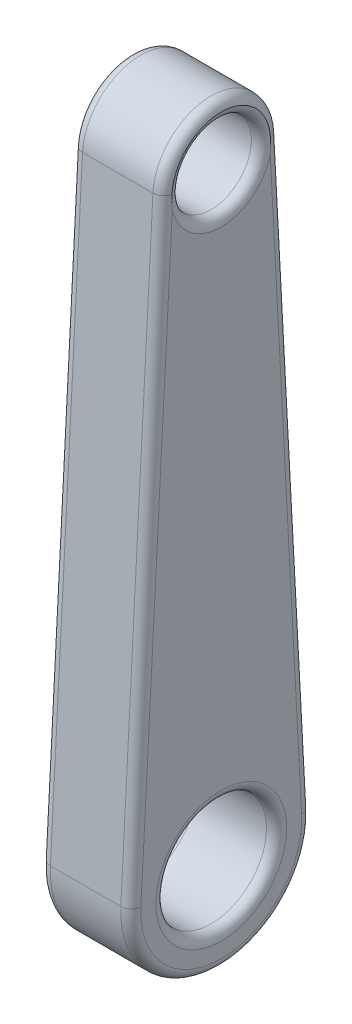
SolidWorks part; units mm, degrees
material "Plain Carbon Steel"
ref_plane "Front Plane" through (0, 0, 0) normal (0, 0, 1) x (1, 0, 0)
ref_plane "Top Plane" through (0, 0, 0) normal (0, 1, 0) x (1, 0, 0)
ref_plane "Right Plane" through (0, 0, 0) normal (1, 0, 0) x (0, 0, -1)
other "Configuration Table"
sketch "Sketch1" plane through (0, 0, 0) normal (1, 0, 0) x (0, 0, -1)
  line L0 (0, 55) -> (0, -55) construction
  line L1 (-7.3555, 76.5929) -> (-11.4137, 0.6096)
  line L2 (11.4137, 0.6096) -> (7.3555, 76.5929)
  circle A0 centre (0, 0) radius 6.985
  arc A1 (-11.4137, 0.6096) -> (11.4137, 0.6096) centre (0, 0) ccw
  circle A2 centre (0, 76.2) radius 5.08
  arc A3 (7.3555, 76.5929) -> (-7.3555, 76.5929) centre (0, 76.2) ccw
  dimension "D1" = 13.97
  dimension "D2" = 76.2
  dimension "D3" = 10.16
  dimension "D4" = 14.732
  dimension "D5" = 22.86
extrude "Boss-Extrude1" add sketch "Sketch1" along normal mid plane 11.43
fillet "Fillet1" radius 1.27 12 edges at (-5.715, 38.6012, -9.3846) (-5.715, 76.2, -5.08) (5.715, 76.2, -5.08) (-5.715, 0, -6.985) (5.715, 0, -6.985) (-5.715, 83.566, 0) (-5.715, 38.6012, 9.3846) (-5.715, -11.43, 0) (5.715, 83.566, 0) (5.715, 38.6012, 9.3846) (5.715, -11.43, 0) (5.715, 38.6012, -9.3846)
